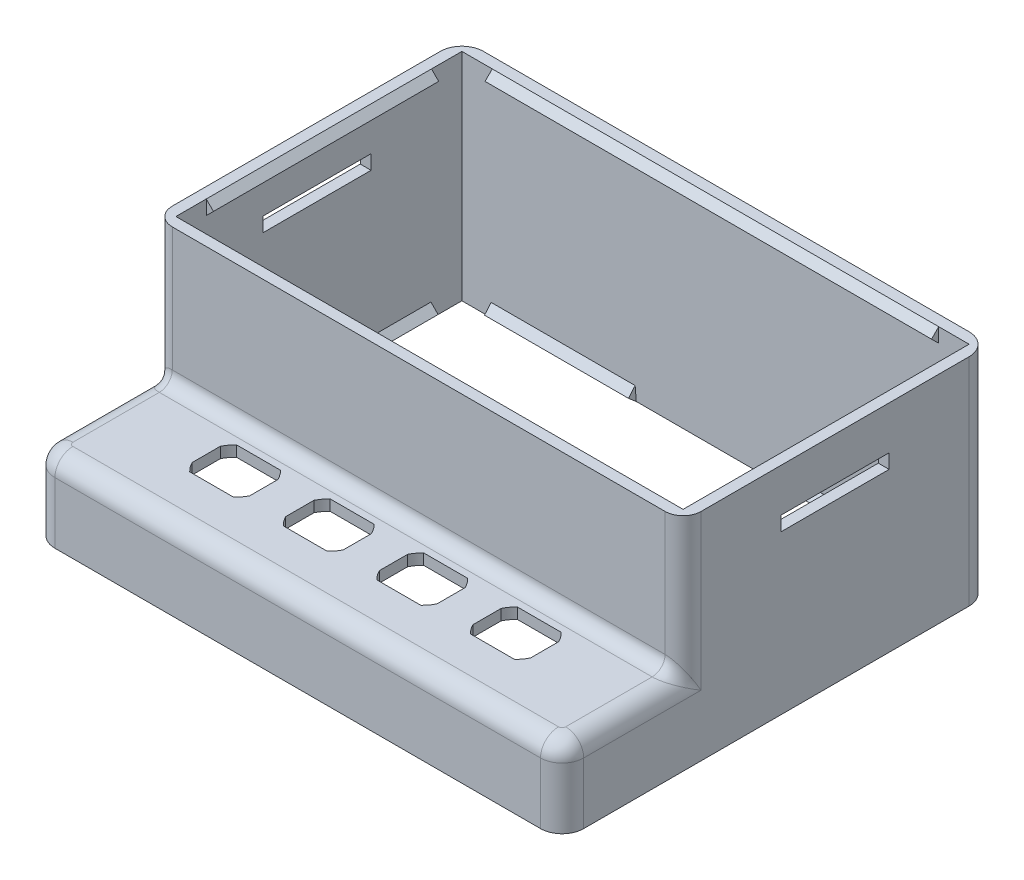
SolidWorks part; units mm, degrees
ref_plane "Front Plane" through (0, 0, 0) normal (0, 0, 1) x (1, 0, 0)
ref_plane "Top Plane" through (0, 0, 0) normal (0, 1, 0) x (1, 0, 0)
ref_plane "Right Plane" through (0, 0, 0) normal (1, 0, 0) x (0, 0, -1)
sketch "Sketch1" plane through (0, 0, 0) normal (0, 1, 0) x (1, 0, 0)
  line L0 (-35.22, -28.26) -> (-35.22, 28.26)
  line L1 (-36.72, -29.76) -> (36.72, -29.76)
  line L2 (-36.72, -29.76) -> (-36.72, 29.76)
  line L3 (-36.72, 29.76) -> (36.72, 29.76)
  line L4 (36.72, -29.76) -> (36.72, 29.76)
  line L5 (-36.72, -29.76) -> (36.72, 29.76) construction
  line L6 (-36.72, 29.76) -> (36.72, -29.76) construction
  line L7 (-35.22, 28.26) -> (35.22, 28.26)
  line L8 (35.22, -28.26) -> (35.22, 28.26)
  line L9 (-35.22, -28.26) -> (35.22, -28.26)
  line L16 (-32.5, -26.46) -> (32.5, -26.46) construction
  line L17 (-32.5, -26.46) -> (-32.5, 25.54) construction
  line L22 (-32.5, 25.54) -> (32.5, 25.54) construction
  line L23 (32.5, -26.46) -> (32.5, 25.54) construction
  point P0 (0, 0)
  point P10 (0, 0)
  dimension "D1" = 73.44
  dimension "D2" = 59.52
  dimension "D4" = 52
  dimension "D5" = 65
  dimension "D6" = 3.3
  dimension "D7" = 4.22
  dimension "D3" = 1.5
extrude "Boss-Extrude1" add sketch "Sketch1" along normal blind 30
ref_plane "Plane1" through (0, 11, 0) normal (0, -1, 0) x (-1, 0, 0)
sketch "Sketch3" plane through (0, 11, 0) normal (0, -1, 0) x (-1, 0, 0)
  line L0 (-2.5, -16.9986) -> (-2.5, -20.9214)
  line L1 (-22.5471, -15.71) -> (-16.4529, -15.71)
  line L2 (-23.5, -16.9986) -> (-23.5, -20.9214)
  line L3 (-22.5471, -22.21) -> (-16.4529, -22.21)
  line L4 (-15.5, -16.9986) -> (-15.5, -20.9214)
  line L5 (-23.5, -15.71) -> (-15.5, -22.21) construction
  line L6 (-23.5, -22.21) -> (-15.5, -15.71) construction
  line L7 (-9.5471, -15.71) -> (-3.4529, -15.71)
  line L8 (-9.5471, -22.21) -> (-3.4529, -22.21)
  line L9 (-10.5, -16.9986) -> (-10.5, -20.9214)
  line L10 (10.5, -16.9986) -> (10.5, -20.9214)
  line L11 (3.4529, -15.71) -> (9.5471, -15.71)
  line L12 (3.4529, -22.21) -> (9.5471, -22.21)
  line L13 (2.5, -16.9986) -> (2.5, -20.9214)
  line L14 (23.5, -16.9986) -> (23.5, -20.9214)
  line L15 (16.4529, -15.71) -> (22.5471, -15.71)
  line L16 (16.4529, -22.21) -> (22.5471, -22.21)
  line L17 (15.5, -16.9986) -> (15.5, -20.9214)
  line L19 (35.22, -28.26) -> (-35.22, -28.26) construction
  arc A0 (-22.5471, -15.71) -> (-23.5, -16.9986) centre (-19.5, -18.96) ccw
  arc A1 (-23.5, -20.9214) -> (-22.5471, -22.21) centre (-19.5, -18.96) ccw
  arc A2 (-16.4529, -22.21) -> (-15.5, -20.9214) centre (-19.5, -18.96) ccw
  arc A3 (-15.5, -16.9986) -> (-16.4529, -15.71) centre (-19.5, -18.96) ccw
  arc A4 (-2.5, -16.9986) -> (-3.4529, -15.71) centre (-6.5, -18.96) ccw
  arc A5 (-3.4529, -22.21) -> (-2.5, -20.9214) centre (-6.5, -18.96) ccw
  arc A6 (-10.5, -20.9214) -> (-9.5471, -22.21) centre (-6.5, -18.96) ccw
  arc A7 (-9.5471, -15.71) -> (-10.5, -16.9986) centre (-6.5, -18.96) ccw
  arc A8 (10.5, -16.9986) -> (9.5471, -15.71) centre (6.5, -18.96) ccw
  arc A9 (9.5471, -22.21) -> (10.5, -20.9214) centre (6.5, -18.96) ccw
  arc A10 (2.5, -20.9214) -> (3.4529, -22.21) centre (6.5, -18.96) ccw
  arc A11 (3.4529, -15.71) -> (2.5, -16.9986) centre (6.5, -18.96) ccw
  arc A12 (23.5, -16.9986) -> (22.5471, -15.71) centre (19.5, -18.96) ccw
  arc A13 (22.5471, -22.21) -> (23.5, -20.9214) centre (19.5, -18.96) ccw
  arc A14 (15.5, -20.9214) -> (16.4529, -22.21) centre (19.5, -18.96) ccw
  arc A15 (16.4529, -15.71) -> (15.5, -16.9986) centre (19.5, -18.96) ccw
  point P14 (-19.5, -18.96)
  point P41 (0, 0)
  point P42 (0, 0)
  point P43 (0, 0)
  point P44 (0, 0)
  point P45 (0, 0)
  dimension "D1" = 9.3
  dimension "D2" = 8
  dimension "D3" = 6.5
sketch "Sketch4" plane through (0, 11, 0) normal (0, -1, 0) x (-1, 0, 0)
  line L0 (36.72, 29.76) -> (36.72, -29.76) construction
  line L1 (36.72, -29.76) -> (-36.72, -29.76)
  line L2 (36.72, -29.76) -> (36.72, -12.96)
  line L3 (36.72, -12.96) -> (-36.72, -12.96)
  line L4 (-36.72, -29.76) -> (-36.72, -12.96)
  line L5 (36.72, -29.76) -> (-36.72, -29.76) construction
  line L6 (-36.72, -29.76) -> (-36.72, 29.76) construction
  dimension "D1" = 6
extrude "Boss-Extrude2" add sketch "Sketch4" along normal blind 1.5
extrude "Cut-Extrude1" cut sketch "Sketch3" along normal blind 1.6
sketch "Sketch5" plane through (36.72, 0, 0) normal (1, 0, 0) x (0, 0, -1)
  line L0 (-32.736, 11) -> (32.736, 11) construction
  line L1 (-29.76, 30) -> (-12.96, 30)
  line L2 (-29.76, 30) -> (-29.76, 11)
  line L3 (-29.76, 11) -> (-12.96, 11)
  line L4 (-12.96, 30) -> (-12.96, 11)
extrude "Cut-Extrude2" cut sketch "Sketch5" against normal through all
sketch "Sketch7" plane through (0, 0, 0) normal (1, 0, 0) x (0, 0, -1)
  line L1 (-12.96, 30) -> (-11.46, 30)
  line L2 (-12.96, 30) -> (-12.96, 9.5)
  line L3 (-12.96, 9.5) -> (-11.46, 9.5)
  line L4 (-11.46, 30) -> (-11.46, 9.5)
  dimension "D1" = 1.5
extrude "Boss-Extrude9" add sketch "Sketch7" along normal through all and the other way through all
ref_plane "Plane2" through (0, 0, 24.04) normal (0, 0, 1) x (1, 0, 0)
sketch "Sketch9" plane through (0, 0, 24.04) normal (0, 0, 1) x (1, 0, 0)
  line L0 (-35.22, 2) -> (-34.22, 1)
  line L1 (-34.22, 1) -> (-35.22, 0)
  line L2 (-35.22, 0) -> (-35.22, 2)
  dimension "D1" = 2
extrude "Boss-Extrude10" add sketch "Sketch9" against normal blind 48
mirror "Mirror1" about plane through (0, 0, 0) normal (1, 0, 0) of "Boss-Extrude10"
sketch "Sketch10" plane through (0, 0, 0) normal (1, 0, 0) x (0, 0, -1)
  line L1 (-28.26, 0) -> (-26.9368, 0.4991)
  line L2 (-26.9368, 0.4991) -> (-27.4359, 1.8223)
  line L3 (-27.4359, 1.8223) -> (-28.26, 0)
  dimension "D1" = 2
extrude "Boss-Extrude11" add sketch "Sketch10" along normal blind 31 and the other way blind 31 separate body
extrude "Cut-Extrude3" cut sketch "Sketch10<2>" against normal blind 11 and the other way blind 11
sketch "Sketch10<2>" plane through (0, 0, 0) normal (1, 0, 0) x (0, 0, -1) same geometry as "Sketch10"
sketch "Sketch11" plane through (0, 0, 0) normal (1, 0, 0) x (0, 0, -1)
  line L0 (28.099, 2) -> (27.1795, 0.9195)
  line L1 (27.1795, 0.9195) -> (28.26, 0)
  line L2 (28.26, 0) -> (28.099, 2)
  dimension "D1" = 2
extrude "Boss-Extrude12" add sketch "Sketch11" along normal blind 31 and the other way blind 31 separate body
extrude "Cut-Extrude4" cut sketch "Sketch11<2>" against normal blind 11 and the other way blind 11
sketch "Sketch11<2>" plane through (0, 0, 0) normal (1, 0, 0) x (0, 0, -1) same geometry as "Sketch11"
fillet "Fillet1" radius 2.5 5 edges at (36.72, 20.5, 12.96) (36.72, 11, 21.36) (-36.72, 20.5, 12.96) (-36.72, 11, 21.36) (0, 11, 29.76)
fillet "Fillet3" radius 3 6 edges at (-35.9878, 10.2678, 29.0278) (36.72, 15, -29.76) (-36.72, 15, -29.76) (-36.72, 4.25, 29.76) (35.9878, 10.2678, 29.0278) (36.72, 4.25, 29.76)
sketch "Sketch12" plane through (0, 0, 0) normal (1, 0, 0) x (0, 0, -1)
  line L0 (27.26, 29) -> (28.26, 30)
  line L1 (28.26, 30) -> (28.26, 28)
  line L2 (28.26, 28) -> (27.26, 29)
  dimension "D1" = 2
extrude "Boss-Extrude13" add sketch "Sketch12" along normal blind 31 and the other way blind 31
ref_plane "Plane3" through (0, 0, -8.4) normal (0, 0, 1) x (1, 0, 0)
mirror "Mirror2" about plane through (0, 0, -8.4) normal (0, 0, 1) of "Boss-Extrude13"
sketch "Sketch14" plane through (0, 0, -8.4) normal (0, 0, 1) x (1, 0, 0)
  line L0 (35.22, 30) -> (34.22, 29)
  line L1 (34.22, 29) -> (35.22, 28)
  line L2 (35.22, 28) -> (35.22, 30)
  dimension "D1" = 2
extrude "Boss-Extrude14" add sketch "Sketch14" along normal blind 15.64 and the other way blind 15.64
mirror "Mirror3" about plane through (0, 0, 0) normal (1, 0, 0) of "Boss-Extrude14"
sketch "Sketch15" plane through (-36.72, 0, 0) normal (-1, 0, 0) x (0, 0, 1)
  line L0 (-26.76, 30) -> (10.46, 30) construction
  line L1 (-15.65, 24) -> (-0.65, 24)
  line L2 (-15.65, 24) -> (-15.65, 22)
  line L3 (-15.65, 22) -> (-0.65, 22)
  line L4 (-0.65, 24) -> (-0.65, 22)
  line L5 (-15.65, 24) -> (-0.65, 22) construction
  line L6 (-15.65, 22) -> (-0.65, 24) construction
  point P0 (-8.15, 23)
  point P7 (-8.15, 30)
  dimension "D1" = 2
  dimension "D2" = 15
  dimension "D3" = 8
extrude "Cut-Extrude5" cut sketch "Sketch15" against normal through all
fillet "Fillet4" radius 1.8 3 edges at (-35.9878, 10.2678, 12.2278) (35.9878, 10.2678, 12.2278) (0, 11, 12.96)
